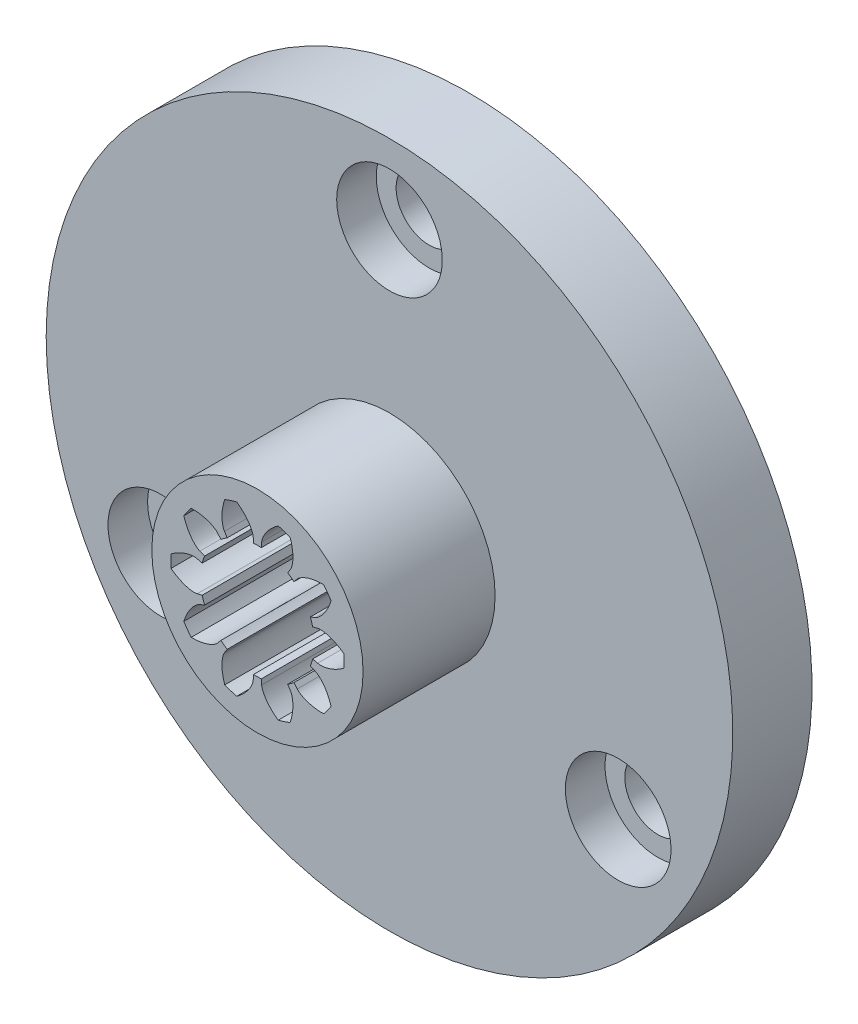
SolidWorks part; units mm, degrees
ref_plane "前视基准面" through (0, 0, 0) normal (0, 0, 1) x (1, 0, 0)
ref_plane "上视基准面" through (0, 0, 0) normal (0, 1, 0) x (1, 0, 0)
ref_plane "右视基准面" through (0, 0, 0) normal (1, 0, 0) x (0, 0, -1)
other "Configuration Table"
sketch "草图1" plane through (0, 0, 0) normal (0, 0, 1) x (1, 0, 0)
  line L0 (0, 0) -> (2.4309, 0.5836) construction
  line L1 (0, 0) -> (2.2784, 0.5724)
  line L2 (0, 0) -> (2.2784, -0.5724)
  line L3 (0, 0) -> (2.4309, -0.5836) construction
  line L4 (0, 0) -> (3.2812, 0) construction
  line L5 (2.4309, 0.5836) -> (2.4309, -0.5836) construction
  circle A0 centre (0, 0) radius 2.1562
  circle A1 centre (0, 0) radius 3.2812
  circle A2 centre (0, 0) radius 2.3492 construction
  circle A3 centre (0, 0) radius 2.5 construction
  circle A4 centre (0, 0) radius 4
  spline S0 degree 4 poles (2.2784, 0.5724) (2.2958, 0.5768) (2.3452, 0.5853) (2.4413, 0.5868) (2.5958, 0.5679) (2.7903, 0.5124) (3.0272, 0.4066) (3.2834, 0.2421) (3.5358, 0.0231) (3.7727, -0.2483) (3.974, -0.5466) (4.1404, -0.8657) (4.2789, -1.2169) (4.4043, -1.6673) (4.4838, -2.22) (4.4818, -2.869) (4.3677, -3.5809) (4.1531, -4.2686) (3.8468, -4.921) (3.4615, -5.5284) (3.0029, -6.0852) (2.4873, -6.5838) (1.9121, -7.024) (1.3827, -7.3498) (0.8874, -7.5945) (0.5232, -7.7483) (0.1923, -7.8681) (-0.0295, -7.9394) (-0.3453, -8.0307) (-0.5876, -8.0859) (-0.8308, -8.1386) (-0.9552, -8.1576) (-1.0347, -8.1719) knots 0 0 0 0 0 0.005604 0.015718 0.02996 0.048734 0.068727 0.096889 0.125051 0.153212 0.181374 0.209535 0.237696 0.271429 0.327752 0.384075 0.440398 0.496721 0.553044 0.609367 0.66569 0.722013 0.778336 0.834659 0.86282 0.890982 0.909091 0.931818 0.954545 0.977273 1 1 1 1 1 construction
  spline S1 degree 4 poles (2.2784, 0.5724) (2.2958, 0.5768) (2.3452, 0.5853) (2.4413, 0.5868) (2.5958, 0.5679) (2.7903, 0.5124) (3.0272, 0.4066) (3.2834, 0.2421) (3.5358, 0.0231) (3.7727, -0.2483) (3.974, -0.5466) (4.1404, -0.8657) (4.2789, -1.2169) (4.4043, -1.6673) (4.4838, -2.22) (4.4818, -2.869) (4.3677, -3.5809) (4.1531, -4.2686) (3.8468, -4.921) (3.4615, -5.5284) (3.0029, -6.0852) (2.4873, -6.5838) (1.9121, -7.024) (1.3827, -7.3498) (0.8874, -7.5945) (0.5232, -7.7483) (0.2697, -7.8401) (0.1427, -7.883) (0.0928, -7.8992) knots 0 0 0 0 0 0.005604 0.015718 0.02996 0.048734 0.068727 0.096889 0.125051 0.153212 0.181374 0.209535 0.237696 0.271429 0.327752 0.384075 0.440398 0.496721 0.553044 0.609367 0.66569 0.722013 0.778336 0.834659 0.86282 0.890982 0.909091 0.909091 0.909091 0.909091 0.909091
  spline S2 degree 4 poles (2.2784, -0.5724) (2.2958, -0.5768) (2.3452, -0.5853) (2.4413, -0.5868) (2.5958, -0.5679) (2.7903, -0.5124) (3.0272, -0.4066) (3.2834, -0.2421) (3.5358, -0.0231) (3.7727, 0.2483) (3.974, 0.5466) (4.1404, 0.8657) (4.2789, 1.2169) (4.4043, 1.6673) (4.4838, 2.22) (4.4818, 2.869) (4.3677, 3.5809) (4.1531, 4.2686) (3.8468, 4.921) (3.4615, 5.5284) (3.0029, 6.0852) (2.4873, 6.5838) (1.9121, 7.024) (1.3827, 7.3498) (0.8874, 7.5945) (0.5232, 7.7483) (0.1923, 7.8681) (-0.0295, 7.9394) (-0.3453, 8.0307) (-0.5876, 8.0859) (-0.8308, 8.1386) (-0.9552, 8.1576) (-1.0347, 8.1719) knots 0 0 0 0 0 0.005604 0.015718 0.02996 0.048734 0.068727 0.096889 0.125051 0.153212 0.181374 0.209535 0.237696 0.271429 0.327752 0.384075 0.440398 0.496721 0.553044 0.609367 0.66569 0.722013 0.778336 0.834659 0.86282 0.890982 0.909091 0.931818 0.954545 0.977273 1 1 1 1 1 construction
  spline S3 degree 4 poles (2.2784, -0.5724) (2.2958, -0.5768) (2.3452, -0.5853) (2.4413, -0.5868) (2.5958, -0.5679) (2.7903, -0.5124) (3.0272, -0.4066) (3.2834, -0.2421) (3.5358, -0.0231) (3.7727, 0.2483) (3.974, 0.5466) (4.1404, 0.8657) (4.2789, 1.2169) (4.4043, 1.6673) (4.4838, 2.22) (4.4818, 2.869) (4.3677, 3.5809) (4.1531, 4.2686) (3.8468, 4.921) (3.4615, 5.5284) (3.0029, 6.0852) (2.4873, 6.5838) (1.9121, 7.024) (1.3827, 7.3498) (0.8874, 7.5945) (0.5232, 7.7483) (0.2697, 7.8401) (0.1427, 7.883) (0.0928, 7.8992) knots 0 0 0 0 0 0.005604 0.015718 0.02996 0.048734 0.068727 0.096889 0.125051 0.153212 0.181374 0.209535 0.237696 0.271429 0.327752 0.384075 0.440398 0.496721 0.553044 0.609367 0.66569 0.722013 0.778336 0.834659 0.86282 0.890982 0.909091 0.909091 0.909091 0.909091 0.909091
  point P16 (2.4309, 0)
  dimension "内啮合齿顶圆直径" = 4.3125
  dimension "内啮合分度圆直径" = 5
  dimension "内啮合基圆直径" = 4.6985
  dimension "内啮合齿根圆直径" = 6.5625
  dimension "外径" = 8
  dimension "渐开线镜像线夹角" = 13.5
extrude "凸台-拉伸1" add sketch "草图1" along normal blind 5 contours A4 | A0
extrude "切除-拉伸2" cut sketch "草图1<3>" along normal through all contours A0 S3 A1 S1 region at (2.6436, 0, 0)
sketch "草图1<3>" plane through (0, 0, 0) normal (0, 0, 1) x (1, 0, 0) same geometry as "草图1"
pattern_circular "阵列(圆周)1" count 10 over 360 about axis through (0, 0, 5) along (0, 0, 1) of "切除-拉伸2"
sketch "草图2" plane through (0, 0, 0) normal (0, 0, -1) x (-1, 0, 0)
  circle A0 centre (0, 0) radius 13
  circle A1 centre (0, 10) radius 2
  circle A2 centre (0, 10) radius 1.25
  circle A3 centre (0, 0) radius 1.6
  dimension "D1" = 26
  dimension "D3" = 4
  dimension "D4" = 2.5
  dimension "D5" = 3.2
  dimension "D2" = 10
extrude "凸台-拉伸2" add sketch "草图2" along normal blind 3 contours A0 | A3
extrude "切除-拉伸4" cut sketch "草图2<3>" along normal through all contours A2
sketch "草图2<3>" plane through (0, 0, 0) normal (0, 0, -1) x (-1, 0, 0) same geometry as "草图2"
extrude "切除-拉伸5" cut sketch "草图2<4>" along normal offset from surface (1.5 mm away) 1.5 contours A1 up to face at (-1.25, 10, 0)
sketch "草图2<4>" plane through (0, 0, 0) normal (0, 0, -1) x (-1, 0, 0) same geometry as "草图2"
pattern_circular "阵列(圆周)2" count 3 over 360 about axis through (0, 0, -3) along (0, 0, 1) of "切除-拉伸5", "切除-拉伸4" reverse direction yes
sketch "草图3" plane through (0, 0, -3) normal (0, 0, -1) x (-1, 0, 0)
  circle A0 centre (0, 0) radius 2.55
  dimension "D1" = 5.1
extrude "切除-拉伸6" cut sketch "草图3" against normal blind 2.6
equation "\"m\"= 0.5'模数"
equation "\"z1\"= 7'外啮合齿轮数"
equation "\"a\"= 20度'压力角"
equation "\"z2\"= 10'内啮合齿轮数"
equation "\"hax\"= 1'齿顶高系数"
equation "\"cx\"= 0.25'顶隙系数"
equation "\"ha\"= \"hax\" * \"m\"'齿顶高"
equation "\"hf\"= ( \"hax\" + \"cx\" ) * \"m\"'齿根高"
equation "\"d1\"= \"m\" * \"z1\"'外啮合分度圆直径"
equation "\"da1\"= ( \"z1\" + 2 ) * \"m\"'外啮合齿顶圆直径"
equation "\"df1\"= \"d1\" - 2 * \"hf\"'外啮合齿根圆直径"
equation "\"db1\"= \"d1\" * cos ( \"a\" )'外啮合基圆直径"
equation "\"p\"= \"m\" * PI'齿距"
equation "\"d2\"= \"m\" * \"z2\"'内啮合分度圆直径"
equation "\"db2\"= \"d2\" * cos ( \"a\" )'内啮合基圆直径"
equation "\"da2\"= ( \"z2\" - 2 ) * \"m\"'内啮合齿顶圆直径"
equation "\"df2\"= \"d2\" + 2 * \"hf\"'内啮合齿根圆直径"
equation "\"内啮合齿顶圆直径@草图1\" = \"da2\" + 0.5 * \"hf\""
equation "\"内啮合齿根圆直径@草图1\"= \"df2\" + 0.5 * \"hf\""
equation "\"内啮合分度圆直径@草图1\"= \"d2\""
equation "\"内啮合基圆直径@草图1\"= \"db2\""
equation "\"渐开线镜像线夹角@草图1\"= 360度 / 4 / \"z2\" + 360度 / 4 / \"z2\" / 2"
equation "\"h\"= 5'厚度"
equation "\"外径@草图1\"= 8"
equation "\"厚度@凸台-拉伸1\"= \"h\""
equation "\"内啮合齿轮数@阵列(圆周)1\"= \"z2\""
equation "\"edo\"= 6 '期望的外圈直径"
equation "\"do\"= IIF ( \"edo\" >= ( \"df2\" + 1 ) , \"edo\" , ( \"df2\" + 1 ) )"
